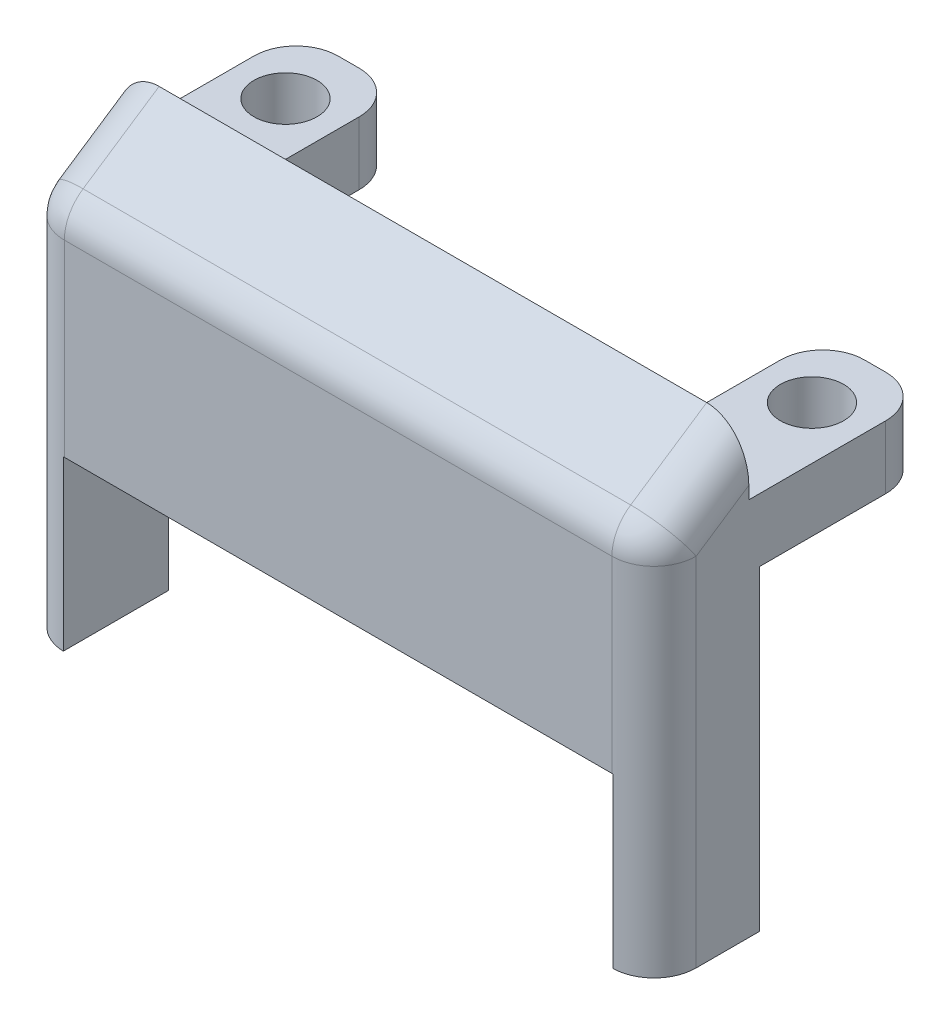
SolidWorks part; units mm, degrees
material "ABS"
ref_plane "Front Plane" through (0, 0, 0) normal (0, 0, 1) x (1, 0, 0)
ref_plane "Top Plane" through (0, 0, 0) normal (0, 1, 0) x (1, 0, 0)
ref_plane "Right Plane" through (0, 0, 0) normal (1, 0, 0) x (0, 0, -1)
sketch "Sketch2" plane through (0, 0, 0) normal (1, 0, 0) x (0, 0, -1)
  line L0 (0, 0) -> (0, 4)
  line L1 (0, 4) -> (3, 4)
  line L2 (3, 4) -> (0, 0)
  line L4 (0, 4) -> (5, 4)
  line L5 (0, 4) -> (0, 10)
  line L6 (0, 10) -> (5, 10)
  line L7 (5, 4) -> (5, 10)
  dimension "D1" = 3
  dimension "D2" = 4
  dimension "D3" = 5
  dimension "D4" = 6
extrude "Boss-Extrude1" add sketch "Sketch2" along normal mid plane 26.1 contours L4 L7 L6 L5 L1 | L2 L1 L0 region at (0, 2.6667, -1) region at (0, 7, -2.5)
sketch "Sketch3" plane through (0, 10, 0) normal (0, 1, 0) x (1, 0, 0)
  line L0 (13.05, 5) -> (-13.05, 5) construction
  line L1 (-15, 5) -> (15, 5)
  line L2 (-15, 5) -> (-15, 0)
  line L3 (-15, 0) -> (15, 0)
  line L4 (15, 5) -> (15, 0)
  line L5 (-15, 5) -> (15, 0) construction
  line L6 (-15, 0) -> (15, 5) construction
  line L7 (13.05, 0) -> (-13.05, 0) construction
  line L8 (-13.05, 5) -> (-13.05, 0)
  line L9 (13.05, 5) -> (13.05, 0)
  point P0 (0, 2.5)
  line M3 (-13.05, 5) -> (-13.05, 0)
  line M5 (13.05, 0) -> (13.05, 5)
  dimension "D1" = 30
extrude "Boss-Extrude2" add sketch "Sketch3" against normal blind 18 contours L2 L3 L1 M3 | L4 L1 L3 M5 region at (-14.025, 10, -2.5) region at (14.025, 10, -2.5)
sketch "Sketch4" plane through (0, 10, 0) normal (0, 1, 0) x (1, 0, 0)
  line L5 (0, 0) -> (0, 5) construction
  line L6 (-15, 5) -> (-10, 5)
  line L7 (-15, 5) -> (-15, 13)
  line L8 (-15, 13) -> (-10, 13)
  line L9 (-10, 5) -> (-10, 13)
  line L10 (15, 5) -> (-15, 5) construction
  line L11 (15, 5) -> (10, 5)
  line L12 (15, 5) -> (15, 13)
  line L13 (15, 13) -> (10, 13)
  line L14 (10, 5) -> (10, 13)
  circle A0 centre (-12.5, 10) radius 1.5
  circle A1 centre (12.5, 10) radius 1.5
  point P11 (-12.5, 13)
  dimension "D3" = 3
  dimension "D1" = 8
  dimension "D2" = 5
  dimension "D4" = 3
extrude "Boss-Extrude3" add sketch "Sketch4" against normal blind 3
sketch "Sketch6" plane through (15, 0, 0) normal (1, 0, 0) x (0, 0, -1)
  line L0 (0, 10) -> (4.5, 13)
  line L1 (4.5, 13) -> (4.5, 10)
  line L2 (13, 10) -> (0, 10) construction
  line L4 (0, 10) -> (4.5, 10)
  line L5 (5, -8) -> (5, 7) construction
  dimension "D1" = 3
  dimension "D2" = 0.5
extrude "Boss-Extrude4" add sketch "Sketch6" against normal up to surface (30 mm away) up to face at (-15, 3, -6)
fillet "Fillet2" radius 2 8 edges at (15, 1, 0) (-15, 1, 0) (-15, 8.5, -13) (-10, 8.5, -13) (10, 8.5, -13) (15, 8.5, -13) (-10, 8.5, -5) (10, 8.5, -5)
fillet "Fillet4" radius 2 5 edges at (15, 12.1667, -3.25) (14.4142, 10.3905, -0.5858) (-15, 12.1667, -3.25) (-14.4142, 10.3905, -0.5858) (0, 10, 0)
